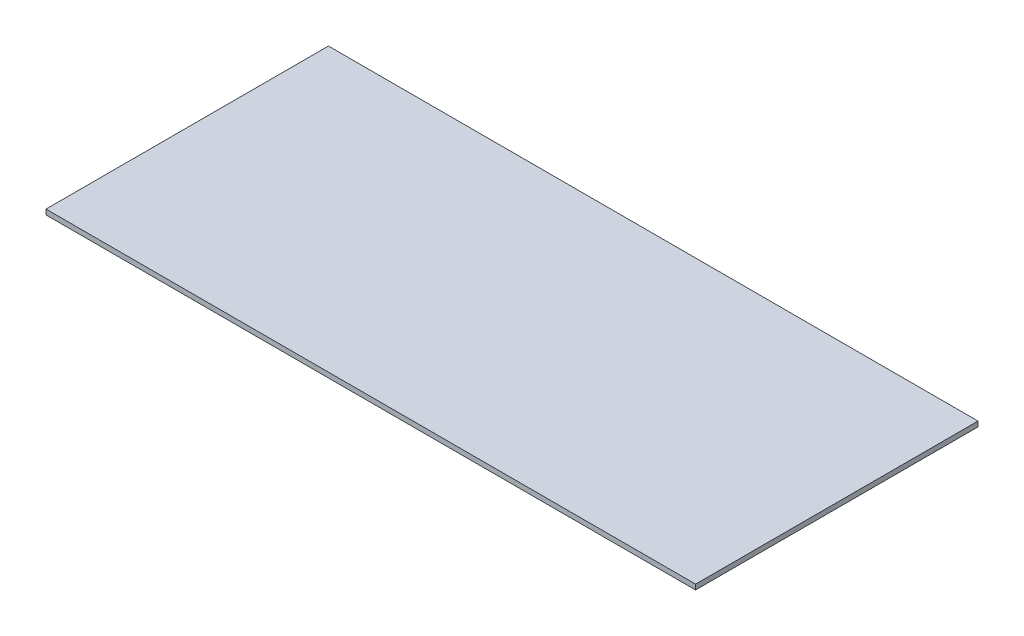
SolidWorks part; units mm, degrees
material "ABS"
ref_plane "Front Plane" through (0, 0, 0) normal (0, 0, 1) x (1, 0, 0)
ref_plane "Top Plane" through (0, 0, 0) normal (0, 1, 0) x (1, 0, 0)
ref_plane "Right Plane" through (0, 0, 0) normal (1, 0, 0) x (0, 0, -1)
sketch "Sketch1" plane through (0, 0, 0) normal (0, 1, 0) x (1, 0, 0)
  line L1 (0, 0) -> (2300, 0)
  line L2 (0, 0) -> (0, 1000)
  line L3 (0, 1000) -> (2300, 1000)
  line L4 (2300, 0) -> (2300, 1000)
  dimension "D1" = 1000
  dimension "D2" = 2300
extrude "Boss-Extrude1" add sketch "Sketch1" along normal blind 18
